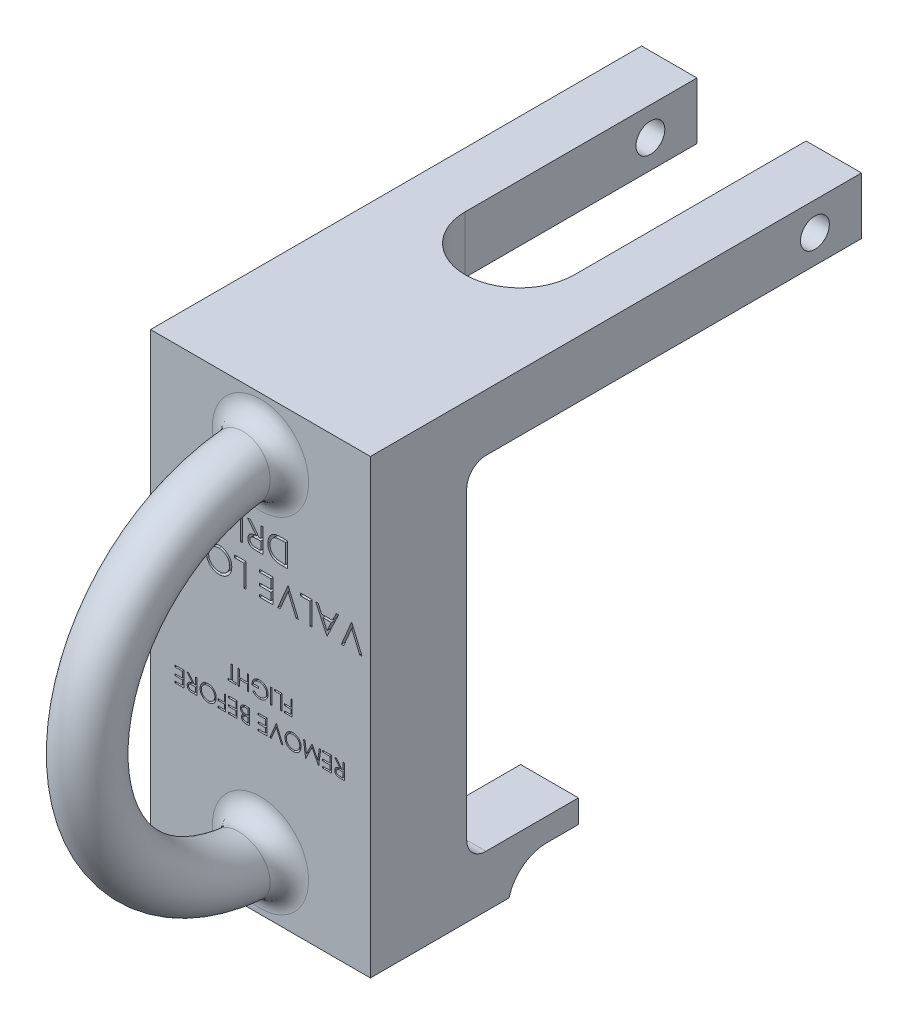
SolidWorks part; units mm, degrees
material "ABS PC"
ref_plane "Front Plane" through (0, 0, 0) normal (0, 0, 1) x (1, 0, 0)
ref_plane "Top Plane" through (0, 0, 0) normal (0, 1, 0) x (1, 0, 0)
ref_plane "Right Plane" through (0, 0, 0) normal (1, 0, 0) x (0, 0, -1)
sketch "Sketch1" plane through (0, 0, 0) normal (0, 0, 1) x (1, 0, 0)
  line L0 (0, 2.5) -> (0, -5) construction
  line L1 (-14.5, -5) -> (14.5, -5)
  line L2 (-14.5, -5) -> (-14.5, 2.5)
  line L3 (-14.5, 2.5) -> (14.5, 2.5)
  line L4 (14.5, -5) -> (14.5, 2.5)
  circle A0 centre (0, 0) radius 1.5
  dimension "D1" = 3
  dimension "D2" = 29
  dimension "D3" = 5
  dimension "D4" = 2.5
extrude "Boss-Extrude2" add sketch "Sketch1" along normal blind 21.59 contours L0 L3 L2 L1 A0 | L0 A0 | A0 L0 | L3 L0 A0 L1 L4 region at (7.4721, -1.292, 0) region at (-7.4721, -1.292, 0) region at (0.6366, 0, 0) region at (-0.6366, 0, 0)
ref_plane "Plane1" through (0, -1.25, 0) normal (0, 1, 0) x (1, 0, 0)
sketch "Sketch15" plane through (0, 2.5, 0) normal (0, 1, 0) x (1, 0, 0)
  line L0 (-14.5, 0) -> (14.5, 0) construction
  line L1 (-14.5, 0) -> (14.5, 0)
  line L3 (-14.5, 0) -> (14.5, 0)
  line L7 (-7.2, 12.61) -> (7.2, 12.61) construction
  line L10 (-14.5, 0) -> (-14.5, 43.18)
  line L11 (-14.5, 43.18) -> (-7.2, 43.18)
  line L12 (-7.2, 12.61) -> (-7.2, 43.18)
  line L14 (7.2, 12.61) -> (7.2, 43.18)
  line L15 (7.2, 43.18) -> (14.5, 43.18)
  line L16 (14.5, 0) -> (14.5, 43.18)
  arc A0 (-7.2, 12.61) -> (7.2, 12.61) centre (0, 12.61) ccw
  line M5 (14.5, 0) -> (-14.5, 0)
  dimension "D2" = 7.2
  dimension "D1" = 43.18
  dimension "D3" = 12.61
extrude "Boss-Extrude3" add sketch "Sketch15" against normal up to surface (7.5 mm away) contours A0 M5 region at (-13.9799, 2.5, -21.59) up to face at (0, -5, 10.795)
sketch "Sketch19" plane through (0, -5, 0) normal (0, 1, 0) x (1, 0, 0)
  line L0 (-6.88, -13.462) -> (6.88, -13.462)
  line L1 (-14.5, -21.59) -> (14.5, -21.59) construction
  line L2 (-6.88, -13.462) -> (-6.88, -8.89)
  line L3 (-6.88, -8.89) -> (-14.5, -8.89)
  line L4 (-14.5, -21.59) -> (-14.5, 43.18) construction
  line L5 (-14.5, -8.89) -> (-14.5, -21.59)
  line L6 (-14.5, -21.59) -> (14.5, -21.59)
  line L7 (14.5, -21.59) -> (14.5, -8.89)
  line L8 (14.5, -21.59) -> (14.5, 43.18) construction
  line L9 (14.5, -8.89) -> (6.88, -8.89)
  line L10 (6.88, -8.89) -> (6.88, -13.462)
  point P10 (0, -13.462)
  point P17 (0, -21.59)
  dimension "D1" = 8.128
  dimension "D2" = 7.62
  dimension "D3" = 12.7
extrude "Boss-Extrude4" add sketch "Sketch19" against normal blind 48.26
sketch "Sketch20" plane through (14.5, 0, 0) normal (1, 0, 0) x (0, 0, -1)
  line L0 (43.18, -5) -> (43.18, 2.5) construction
  circle A0 centre (37.0332, -1.25) radius 1.905
  point P5 (43.18, -1.25)
  dimension "D2" = 3.81
  dimension "D1" = 6.1468
extrude "Cut-Extrude1" cut sketch "Sketch20" against normal through all
fillet "Fillet1" radius 2.54 2 edges at (6.88, -29.13, 13.462) (-6.88, -29.13, 13.462)
fillet "Fillet2" radius 2.54 2 edges at (-10.69, -5, 8.89) (10.69, -5, 8.89)
fillet "Fillet3" radius 2.54 5 edges at (6.88, -5, 8.636) (6.1361, -5, 12.7181) (0, -5, 13.462) (-6.1361, -5, 12.7181) (-6.88, -5, 8.636)
sketch "Sketch21" plane through (0, 0, 8.89) normal (0, 0, -1) x (-1, 0, 0)
  line L0 (14.5, -53.26) -> (14.5, -7.54) construction
  line L1 (6.88, -53.26) -> (14.5, -53.26)
  line L2 (6.88, -53.26) -> (6.88, -50.212)
  line L3 (6.88, -50.212) -> (14.5, -50.212)
  line L4 (14.5, -53.26) -> (14.5, -50.212)
  line L5 (-14.5, -53.26) -> (-14.5, -7.54) construction
  line L6 (-6.88, -53.26) -> (-14.5, -53.26)
  line L7 (-6.88, -53.26) -> (-6.88, -50.212)
  line L8 (-6.88, -50.212) -> (-14.5, -50.212)
  line L9 (-14.5, -53.26) -> (-14.5, -50.212)
  dimension "D1" = 3.048
extrude "Boss-Extrude5" add sketch "Sketch21" along normal blind 14.732
fillet "Fillet4" radius 2.54 2 edges at (-10.69, -50.212, 8.89) (10.69, -50.212, 8.89)
sketch "Sketch29" plane through (0, 0, 21.59) normal (0, 0, 1) x (1, 0, 0)
  line L0 (14.5, -34.21) -> (-14.5, -34.21) construction
  line L1 (14.5, -53.26) -> (14.5, 2.5) construction
  line L2 (-14.5, -53.26) -> (-14.5, 2.5) construction
  line L3 (14.5, -17.7) -> (-14.5, -17.7) construction
  line L4 (14.5, -30.4) -> (-14.5, -30.4) construction
  line L5 (14.5, -12.62) -> (-14.5, -12.62) construction
  line L6 (-14.5, -53.26) -> (14.5, -53.26) construction
  text T0 "REMOVE BEFORE" font "Century Gothic" height 2.032
  text T1 "FLIGHT" font "Century Gothic" height 2.032
  text T2 "VALVE LOCK"
  text T3 "DRL"
  dimension "D1" = 3.81
  dimension "D2" = 19.05
  dimension "D3" = 12.7
  dimension "D4" = 5.08
extrude "Cut-Extrude2" cut sketch "Sketch29" against normal blind 2.54
sketch "Sketch30" plane through (0, -53.26, 0) normal (0, -1, 0) x (1, 0, 0)
  line L0 (-14.5, 3.302) -> (-6.88, 3.302)
  line L1 (6.88, 3.302) -> (14.5, 3.302)
  line L8 (-6.88, -5.842) -> (-6.88, 10.922)
  line L9 (-4.34, 13.462) -> (4.34, 13.462)
  line L10 (6.88, 10.922) -> (6.88, -5.842)
  line L11 (6.88, -5.842) -> (14.5, -5.842)
  line L12 (14.5, -5.842) -> (14.5, 21.59)
  line L13 (14.5, 21.59) -> (-14.5, 21.59)
  line L14 (-14.5, 21.59) -> (-14.5, -5.842)
  line L15 (-14.5, -5.842) -> (-6.88, -5.842)
  line L16 (-6.88, 3.302) -> (-6.88, 10.922)
  line L17 (-4.34, 13.462) -> (4.34, 13.462)
  line L18 (6.88, 10.922) -> (6.88, 3.302)
  line L20 (14.5, 3.302) -> (14.5, 21.59)
  line L21 (14.5, 21.59) -> (-14.5, 21.59)
  line L22 (-14.5, 21.59) -> (-14.5, 3.302)
  arc A2 (-4.34, 13.462) -> (-6.88, 10.922) centre (-4.34, 10.922) ccw
  arc A3 (6.88, 10.922) -> (4.34, 13.462) centre (4.34, 10.922) ccw
  arc A4 (-4.34, 13.462) -> (-6.88, 10.922) centre (-4.34, 10.922) ccw
  arc A5 (6.88, 10.922) -> (4.34, 13.462) centre (4.34, 10.922) ccw
  dimension "D2" = 18.288
  dimension "D1" = 0
extrude "Boss-Extrude6" add sketch "Sketch30" along normal blind 3.81
fillet "Fillet5" radius 5.08 2 edges at (10.69, -53.26, 3.302) (-10.69, -53.26, 3.302)
sketch "Sketch2" plane through (0, -25.38, 0) normal (1, 0, 0) x (0, -1, 0)
  line L1 (31.69, -21.59) -> (-27.88, -21.59) construction
  line L2 (31.69, -21.59) -> (-27.88, -21.59) construction
  arc A0 (-20.955, -21.59) -> (24.765, -21.59) centre (1.905, -21.59) ccw
  point P7 (0, 0)
  point P8 (0, 0)
  point P9 (0, 0)
  point P10 (0, 0)
  point P11 (0, 0)
  dimension "D1" = 22.86
sweep "Sweep1" add path "Sketch2" circular profile diameter 7.62 parameters "D3"=7.62
fillet "Fillet6" radius 2.54 2 edges at (3.81, -50.145, 21.59) (3.81, -4.425, 21.59)
